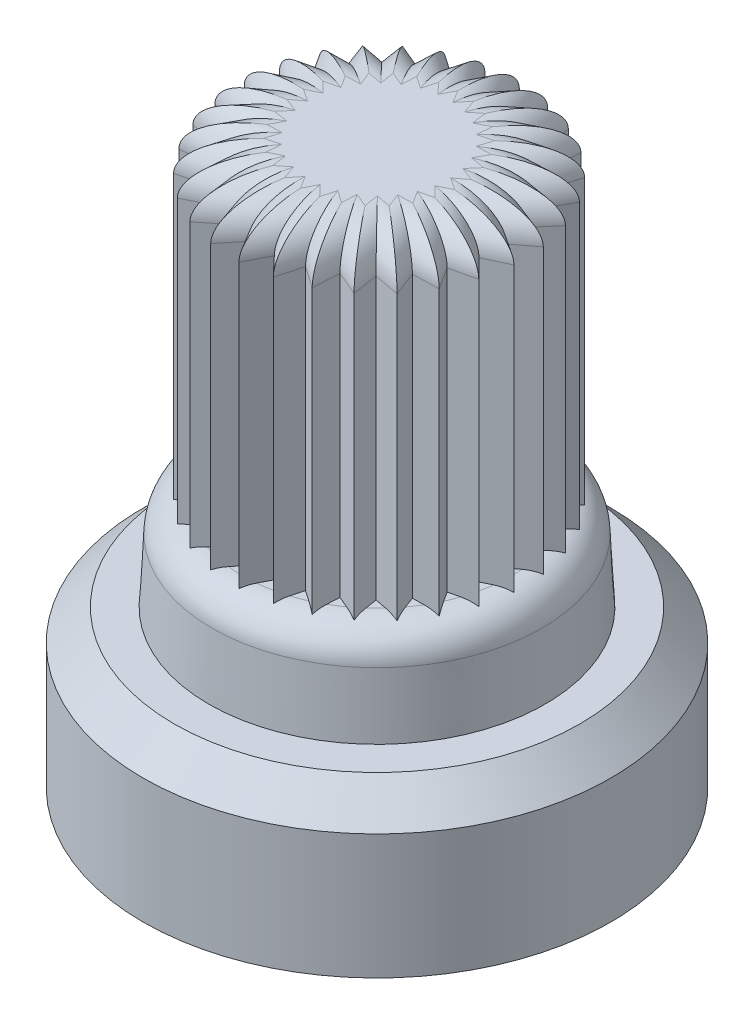
SolidWorks part; units mm, degrees
ref_plane "Спереди" through (0, 0, 0) normal (0, 0, 1) x (1, 0, 0)
ref_plane "Сверху" through (0, 0, 0) normal (0, 1, 0) x (1, 0, 0)
ref_plane "Справа" through (0, 0, 0) normal (1, 0, 0) x (0, 0, -1)
sketch "Sketch1" plane through (0, 0, 0) normal (0, 1, 0) x (1, 0, 0)
  circle A0 centre (0, 0) radius 7.5
  dimension "D1" = 15
extrude "Boss-Extrude1" add sketch "Sketch1" along normal blind 18
sketch "Sketch2" plane through (0, 0, 0) normal (0, -1, 0) x (1, 0, 0)
  circle A0 centre (0, 0) radius 6.5
  dimension "D1" = 13
extrude "Cut-Extrude1" cut sketch "Sketch2" against normal blind 3
sketch "Sketch3" plane through (0, 3, 0) normal (0, -1, 0) x (1, 0, 0)
  line L0 (-1.9498, -2.6624) -> (3.266, -0.4725)
  line L1 (0.6581, -1.5674) -> (-1.2775, 3.0427) construction
  circle A0 centre (0, 0) radius 3.3 construction
  arc A1 (-1.9498, -2.6624) -> (3.266, -0.4725) centre (0, 0) cw
  dimension "D1" = 6.6
  dimension "D2" = 5
extrude "Cut-Extrude2" cut sketch "Sketch3" against normal blind 12
chamfer "Chamfer1" distance 1 angle 30 1 edges at (0, 0, -6.5) first distance on face at (0, 3, -6.5)
sketch "Sketch4" plane through (0, 18, 0) normal (0, 1, 0) x (1, 0, 0)
  circle A0 centre (0, 0) radius 5.5
  dimension "D1" = 11
extrude "Cut-Extrude3" cut sketch "Sketch4" against normal blind 13 flip side to cut
chamfer "Chamfer2" distance 15 angle 3 1 edges at (0, 18, 5.5) first distance on face at (0, 5, 5.5)
chamfer "Chamfer3" distance 1 angle 45 1 edges at (0, 5, 7.5)
sketch "Sketch5" plane through (0, 18, 0) normal (0, 1, 0) x (1, 0, 0)
  line L0 (3.5975, 1.7486) -> (4.4295, 1.6124)
  line L1 (4.4295, 1.6124) -> (3.8798, 0.9732)
  line L2 (3.8798, 0.9732) -> (4.6653, 0.667)
  line L3 (4.6653, 0.667) -> (3.9947, 0.156)
  line L4 (3.9947, 0.156) -> (4.6993, -0.3068)
  line L5 (4.6993, -0.3068) -> (3.9371, -0.6672)
  line L6 (3.9371, -0.6672) -> (4.5302, -1.2664)
  line L7 (4.5302, -1.2664) -> (3.7097, -1.4604)
  line L8 (3.7097, -1.4604) -> (4.1652, -2.1699)
  line L9 (4.1652, -2.1699) -> (3.3223, -2.1891)
  line L10 (3.3223, -2.1891) -> (3.6203, -2.9777)
  line L11 (3.6203, -2.9777) -> (2.7919, -2.8212)
  line L12 (2.7919, -2.8212) -> (2.9195, -3.6546)
  line L13 (2.9195, -3.6546) -> (2.1417, -3.3293)
  line L14 (2.1417, -3.3293) -> (2.0931, -4.171)
  line L15 (2.0931, -4.171) -> (1.4, -3.6911)
  line L16 (1.4, -3.6911) -> (1.1775, -4.5043)
  line L17 (1.1775, -4.5043) -> (0.5993, -3.8908)
  line L18 (0.5993, -3.8908) -> (0.2126, -4.6399)
  line L19 (0.2126, -4.6399) -> (-0.2254, -3.9196)
  line L20 (-0.2254, -3.9196) -> (-0.7594, -4.572)
  line L21 (-0.7594, -4.572) -> (-1.0381, -3.7763)
  line L22 (-1.0381, -3.7763) -> (-1.6961, -4.3035)
  line L23 (-1.6961, -4.3035) -> (-1.8032, -3.4672)
  line L24 (-1.8032, -3.4672) -> (-2.5564, -3.846)
  line L25 (-2.5564, -3.846) -> (-2.4874, -3.0058)
  line L26 (-2.4874, -3.0058) -> (-3.3029, -3.2197)
  line L27 (-3.3029, -3.2197) -> (-3.0607, -2.4122)
  line L28 (-3.0607, -2.4122) -> (-3.9028, -2.4519)
  line L29 (-3.9028, -2.4519) -> (-3.498, -1.7124)
  line L30 (-3.498, -1.7124) -> (-4.33, -1.5762)
  line L31 (-4.33, -1.5762) -> (-3.7802, -0.937)
  line L32 (-3.7802, -0.937) -> (-4.5657, -0.6307)
  line L33 (-4.5657, -0.6307) -> (-3.8951, -0.1198)
  line L34 (-3.8951, -0.1198) -> (-4.5998, 0.3431)
  line L35 (-4.5998, 0.3431) -> (-3.8376, 0.7034)
  line L36 (-3.8376, 0.7034) -> (-4.4306, 1.3027)
  line L37 (-4.4306, 1.3027) -> (-3.6102, 1.4967)
  line L38 (-3.6102, 1.4967) -> (-4.0656, 2.2061)
  line L39 (-4.0656, 2.2061) -> (-3.2228, 2.2253)
  line L40 (-3.2228, 2.2253) -> (-3.5208, 3.014)
  line L41 (-3.5208, 3.014) -> (-2.6924, 2.8575)
  line L42 (-2.6924, 2.8575) -> (-2.8199, 3.6909)
  line L43 (-2.8199, 3.6909) -> (-2.0421, 3.3656)
  line L44 (-2.0421, 3.3656) -> (-1.9936, 4.2072)
  line L45 (-1.9936, 4.2072) -> (-1.3004, 3.7273)
  line L46 (-1.3004, 3.7273) -> (-1.078, 4.5405)
  line L47 (-1.078, 4.5405) -> (-0.4997, 3.927)
  line L48 (-0.4997, 3.927) -> (-0.113, 4.6762)
  line L49 (-0.113, 4.6762) -> (0.325, 3.9558)
  line L50 (0.325, 3.9558) -> (0.859, 4.6082)
  line L51 (0.859, 4.6082) -> (1.1377, 3.8126)
  line L52 (1.1377, 3.8126) -> (1.7956, 4.3397)
  line L53 (1.7956, 4.3397) -> (1.9028, 3.5035)
  line L54 (1.9028, 3.5035) -> (2.656, 3.8823)
  line L55 (2.656, 3.8823) -> (2.587, 3.042)
  line L56 (2.587, 3.042) -> (3.4024, 3.256)
  line L57 (3.4024, 3.256) -> (3.1602, 2.4484)
  line L58 (3.1602, 2.4484) -> (4.0024, 2.4882)
  line L59 (4.0024, 2.4882) -> (3.5975, 1.7486)
  circle A0 centre (0, 0) radius 4 construction
  circle A1 centre (0, 0) radius 4.7139 construction
  point P7 (0, 0)
  point P9 (0, 0)
  point P98 (0.0498, 0.0181)
  dimension "D1" = 8
  dimension "D2" = 30
extrude "Cut-Extrude4" cut sketch "Sketch5" against normal blind 10 flip side to cut
fillet "Fillet1" radius 1 1 edges at (0, 8, 5.238)
fillet "Fillet2" radius 1 60 edges at (4.1547, 18, -1.2928) (4.2726, 18, -0.8201) (4.33, 18, -0.4115) (4.347, 18, 0.0754) (4.3182, 18, 0.487) (4.2337, 18, 0.9668) (4.1199, 18, 1.3634) (3.9375, 18, 1.8152) (3.7438, 18, 2.1795) (3.4713, 18, 2.5834) (3.2061, 18, 2.8995) (2.8557, 18, 3.2379) (2.5306, 18, 3.492) (2.1174, 18, 3.7502) (1.7466, 18, 3.931) (1.2887, 18, 4.0977) (0.8884, 18, 4.1975) (0.4059, 18, 4.2653) (-0.0064, 18, 4.2798) (-0.4924, 18, 4.2458) (-0.8988, 18, 4.1742) (-1.3671, 18, 4.0399) (-1.7497, 18, 3.8853) (-2.1798, 18, 3.6566) (-2.5219, 18, 3.4259) (-2.8951, 18, 3.1128) (-3.1818, 18, 2.816) (-3.4817, 18, 2.4321) (-3.7004, 18, 2.0822) (-3.914, 18, 1.6443) (-4.0551, 18, 1.2566) (-4.173, 18, 0.7838) (-4.2304, 18, 0.3752) (-4.2475, 18, -0.1117) (-4.2187, 18, -0.5233) (-4.1341, 18, -1.0031) (-4.0204, 18, -1.3997) (-3.8379, 18, -1.8514) (-3.6442, 18, -2.2157) (-3.3718, 18, -2.6196) (-3.1066, 18, -2.9357) (-2.7561, 18, -3.2742) (-2.431, 18, -3.5282) (-2.0178, 18, -3.7864) (-1.647, 18, -3.9673) (-1.1892, 18, -4.1339) (-0.7888, 18, -4.2338) (-0.3064, 18, -4.3016) (0.106, 18, -4.316) (0.592, 18, -4.282) (0.9983, 18, -4.2104) (1.4667, 18, -4.0761) (1.8492, 18, -3.9216) (2.2794, 18, -3.6929) (2.6215, 18, -3.4622) (2.9947, 18, -3.149) (3.2813, 18, -2.8522) (3.5813, 18, -2.4683) (3.8, 18, -2.1184) (4.0135, 18, -1.6805)
